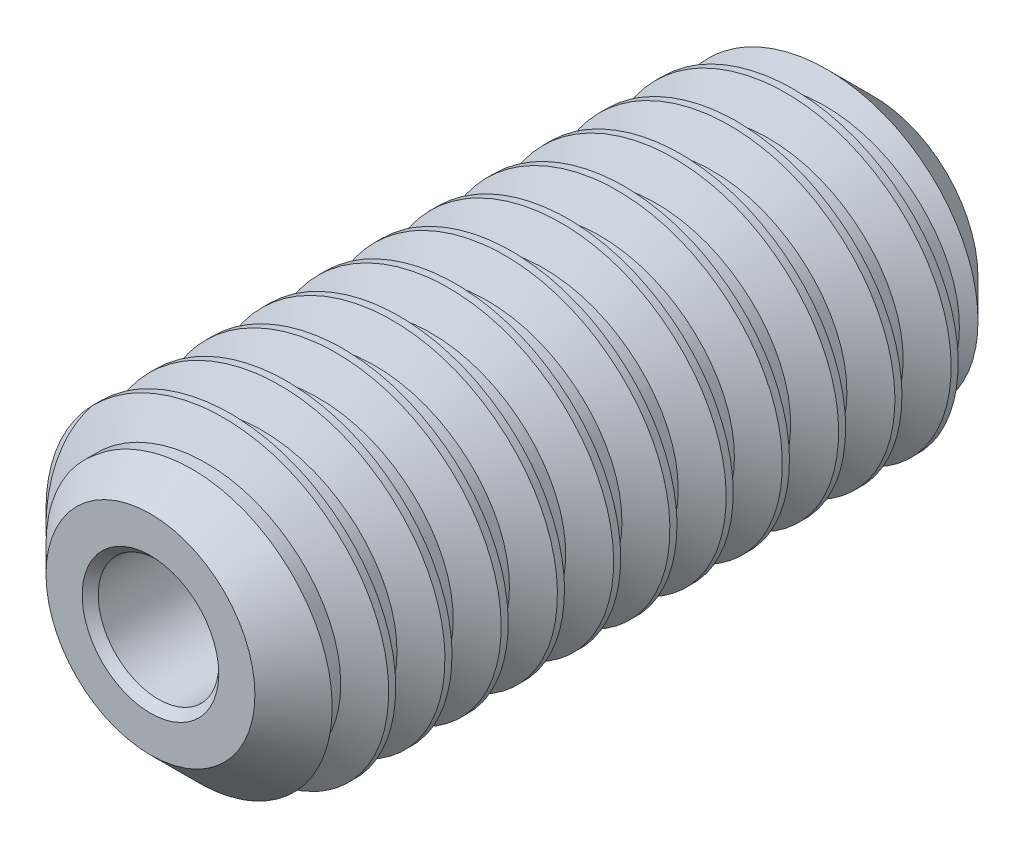
SolidWorks part; units mm, degrees
material "Plain Carbon Steel"
ref_plane "Front Plane" through (0, 0, 0) normal (0, 0, 1) x (1, 0, 0)
ref_plane "Top Plane" through (0, 0, 0) normal (0, 1, 0) x (1, 0, 0)
ref_plane "Right Plane" through (0, 0, 0) normal (1, 0, 0) x (0, 0, -1)
sketch "Brezon Profile" plane through (0, 0, 0) normal (0, 0, 1) x (1, 0, 0)
  circle A0 centre (0, 0) radius 2
  dimension "D1" = 4
extrude "Brezon Body" add sketch "Brezon Profile" against normal blind 9
chamfer "Aesthetic Chamfer" distance 0.7 angle 45 2 edges at (2, 0, 0) (2, 0, -9)
hole_wizard "Grease Hole" positions "Sketch2" profile "Sketch3" hole size "Ø1.5" standard "ISO" end condition through all
sketch "Sketch2" plane through (0, 0, 0) normal (0, 0, 1) x (1, 0, 0)
  point P0 (0, 0)
sketch "Sketch3" plane through (0, 0, 0) normal (1, 0, 0) x (0, -1, 0)
  line L0 (0, 0) -> (0, 9)
  line L1 (0, 9) -> (0.85, 9)
  line L2 (0.75, 8.9) -> (0.75, 0.1)
  line L3 (0.75, 0.1) -> (0.85, 0)
  line L5 (0.85, 0) -> (0, 0)
  line L6 (-0.75, 0.1) -> (-0.85, 0) construction
  line L7 (0.85, 9) -> (0.75, 8.9)
  line L8 (-0.85, 9) -> (-0.75, 8.9) construction
  line L11 (0, -6.35) -> (0, 107.95) construction
  dimension "Thru Hole Dia." = 1.5
  dimension "Thru Hole Depth" = 9
  dimension "Near C'Sink Dia." = 1.7
  dimension "Near C'Sink Angle" = 90
  dimension "Far C'Sink Dia." = 1.7
  dimension "Far C'Sink Angle" = 90
thread "Thread M4x0.7" pitch 0.7 method cut profile "Thread Profile1" start angle 0, offset 1.4, length 15, pitch 0.7, diameter 4
ref_plane "Plane1" through (-2, 0, 0.7) normal (0, -1, 0) x (-1, 0, 0)
sketch "Thread Profile1" plane through (-2, 0, 0.7) normal (0, -1, 0) x (-1, 0, 0)
  line L0 (0, 0) -> (0, 0.7) construction
  line L11 (0, 0) -> (0, 0.6125)
  line L12 (0, 0.6125) -> (-0.3789, 0.3937)
  line L13 (-0.3789, 0.3937) -> (-0.3789, 0.2187)
  line L15 (-0.3789, 0.2187) -> (0, 0)
  line L17 (-0.3789, 0.3062) -> (0, 0.3062) construction
  point P2 (0, 0)
  dimension "Pitch" = 0.7
  dimension "Profile_Angle" = 60
  dimension "Profile_Land" = 0.175
  dimension "Profile_Height" = 0.3789
